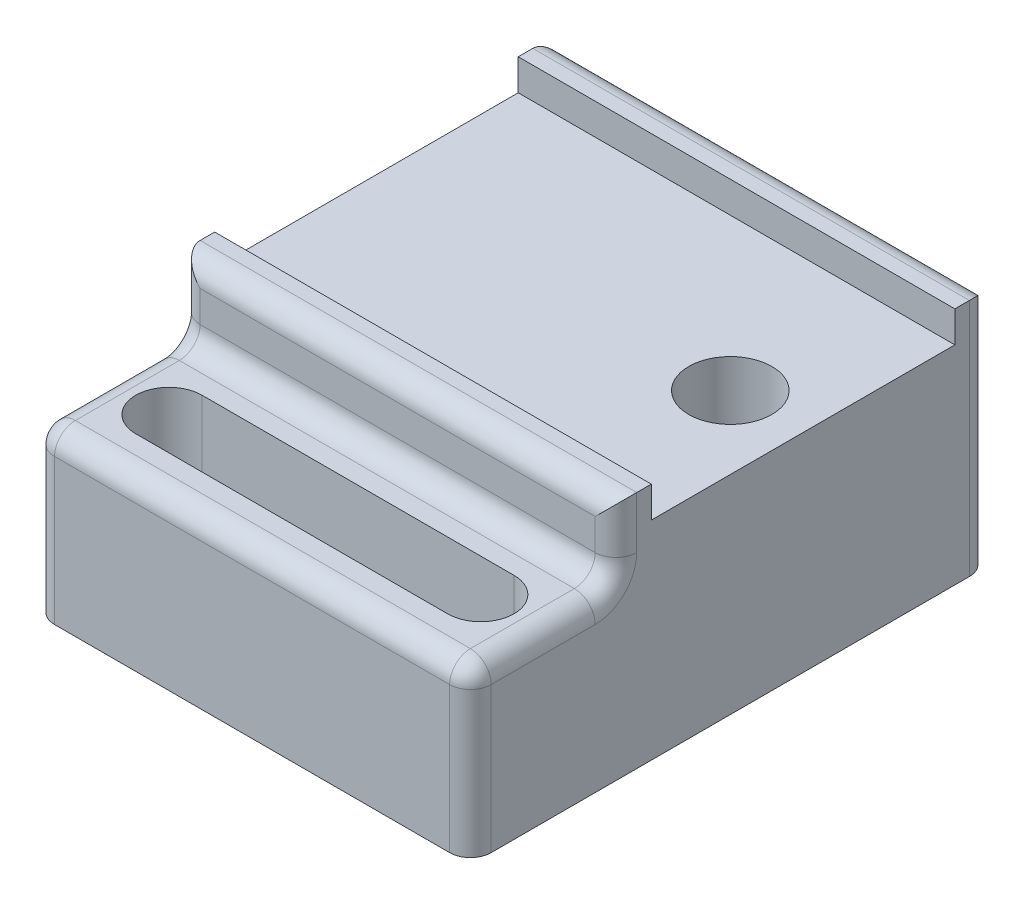
SolidWorks part; units mm, degrees
ref_plane "Front Plane" through (0, 0, 0) normal (0, 0, 1) x (1, 0, 0)
ref_plane "Top Plane" through (0, 0, 0) normal (0, 1, 0) x (1, 0, 0)
ref_plane "Right Plane" through (0, 0, 0) normal (1, 0, 0) x (0, 0, -1)
sketch "Sketch1" plane through (0, 0, 0) normal (0, 1, 0) x (1, 0, 0)
  line L1 (-10.5, 7.3) -> (10.5, 7.3)
  line L2 (-10.5, 7.3) -> (-10.5, -7.3)
  line L3 (-10.5, -7.3) -> (10.5, -7.3)
  line L4 (10.5, 7.3) -> (10.5, -7.3)
  line L5 (-10.5, 7.3) -> (10.5, -7.3) construction
  line L6 (-10.5, -7.3) -> (10.5, 7.3) construction
  line L7 (-10.5, 9) -> (10.5, 9)
  line L8 (-10.5, 9) -> (-10.5, -9)
  line L9 (-10.5, -9) -> (10.5, -9)
  line L10 (10.5, 9) -> (10.5, -9)
  line L11 (-10.5, 9) -> (10.5, -9) construction
  line L12 (-10.5, -9) -> (10.5, 9) construction
  point P0 (0, 0)
  point P6 (0, 0)
  dimension "D1" = 21
  dimension "D2" = 14.6
  dimension "D3" = 18
extrude "Boss-Extrude1" add sketch "Sketch1" along normal blind 10 contours L4 L1 L2 L3 region at (0, 0, 0)
extrude "Boss-Extrude2" add sketch "Sketch1<3>" along normal blind 11.5 contours L10 L3 L8 L9 | L10 L7 L8 L1 region at (0, 0, -8.15) region at (0, 0, 8.15)
sketch "Sketch1<3>" plane through (0, 0, 0) normal (0, 1, 0) x (1, 0, 0) same geometry as "Sketch1"
sketch "Sketch3" plane through (0, 0, 0) normal (0, 1, 0) x (1, 0, 0)
  line L1 (-10.5, -9) -> (10.5, -9)
  line L2 (-10.5, -9) -> (-10.5, -16)
  line L3 (-10.5, -16) -> (10.5, -16)
  line L4 (10.5, -9) -> (10.5, -16)
  dimension "D1" = 7
extrude "Boss-Extrude4" add sketch "Sketch3" along normal blind 8
fillet "Fillet1" radius 1 12 edges at (10.5, 8, 12.5) (-10.5, 9.75, 9) (10.5, 5.75, -9) (0, 11.5, 9) (-10.5, 5.75, -9) (0, 11.5, -9) (-10.5, 4, 16) (10.5, 4, 16) (0, 8, 16) (10.5, 9.75, 9) (-10.5, 8, 12.5) (0, 8, 9)
sketch "Sketch4" plane through (0, 8, 0) normal (0, 1, 0) x (1, 0, 0)
  line L0 (-9.5, -12.5) -> (9.5, -12.5) construction
  line L1 (-9.5, -10) -> (-9.5, -15) construction
  line L2 (9.5, -15) -> (9.5, -10) construction
  line L3 (-7.5, -12.5) -> (7.5, -12.5) construction
  line L4 (-7.5, -10.9) -> (7.5, -10.9)
  line L5 (-7.5, -14.1) -> (7.5, -14.1)
  arc A0 (-7.5, -10.9) -> (-7.5, -14.1) centre (-7.5, -12.5) ccw
  arc A1 (7.5, -14.1) -> (7.5, -10.9) centre (7.5, -12.5) ccw
  point P8 (0, -12.5)
  dimension "D3" = 1.6
  dimension "D1" = 2
  dimension "D2" = 2
extrude "Cut-Extrude1" cut sketch "Sketch4" against normal through all
sketch "Sketch5" plane through (0, 10, 0) normal (0, 1, 0) x (1, 0, 0)
  line L0 (10.5, 7.3) -> (10.5, -7.3) construction
  circle A0 centre (7, 0) radius 2
  point P2 (0, 0)
  point P6 (0, 0)
  dimension "D1" = 4
  dimension "D2" = 3.5
extrude "Cut-Extrude2" cut sketch "Sketch5" against normal blind 6.8
